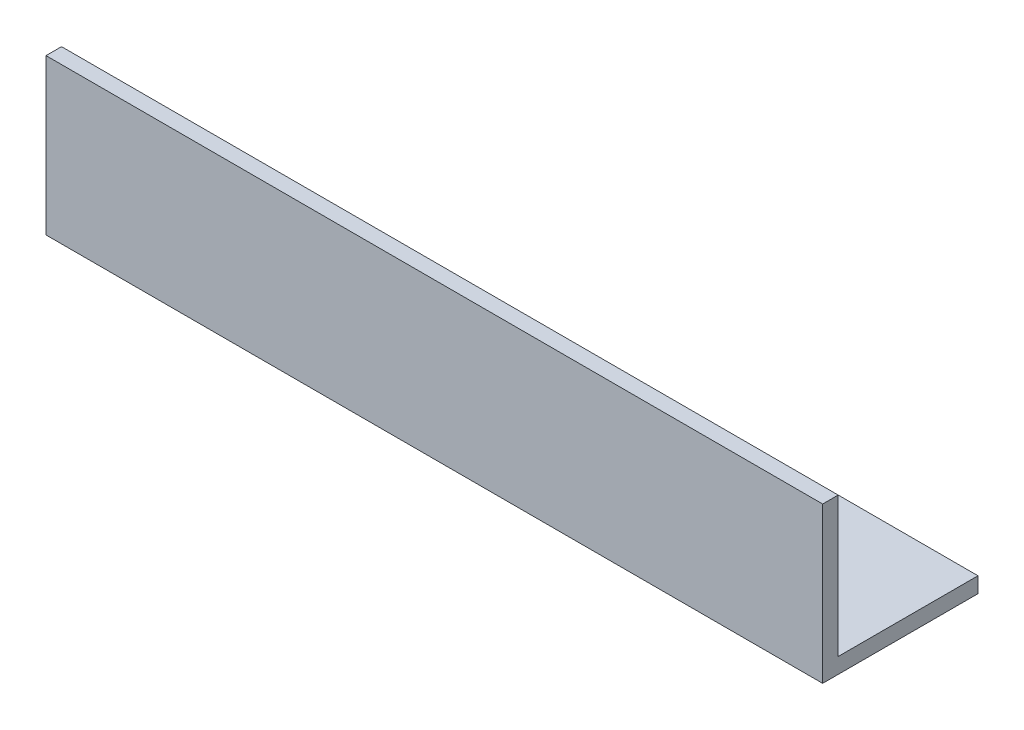
SolidWorks part; units mm, degrees
ref_plane "Спереди" through (0, 0, 0) normal (0, 0, 1) x (1, 0, 0)
ref_plane "Сверху" through (0, 0, 0) normal (0, 1, 0) x (1, 0, 0)
ref_plane "Справа" through (0, 0, 0) normal (1, 0, 0) x (0, 0, -1)
sketch "Эскиз1" plane through (0, 0, 0) normal (1, 0, 0) x (0, 0, -1)
  line L0 (0, 0) -> (0, 30)
  line L1 (0, 0) -> (30, 0)
extrude "Вытянуть-Тонкостенный1" add sketch "Эскиз1" along normal blind 150 thin thin type one direction reverse wall 3
sketch "Эскиз2" plane through (0, 0, 0) normal (0, -1, 0) x (1, 0, 0)
  line L0 (75, -34.5488) -> (75, 3.8648) construction
  circle A0 centre (130, -15) radius 5
  circle A1 centre (100, -15) radius 5
  circle A2 centre (50, -15) radius 5
  circle A3 centre (20, -15) radius 5
  dimension "D1" = 2
extrude "Вырез-Вытянуть1" cut sketch "Эскиз2" against normal through all
